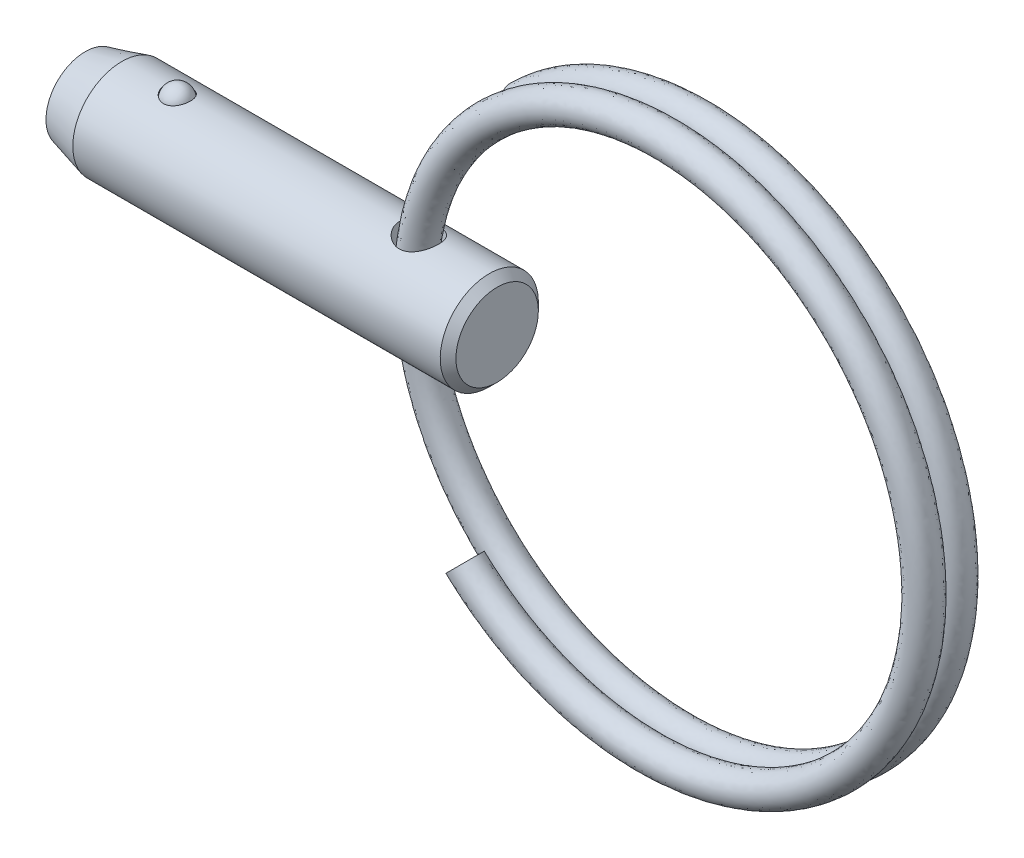
SolidWorks part; units mm, degrees
ref_plane "Front" through (0, 0, 0) normal (0, 0, 1) x (1, 0, 0)
ref_plane "Top" through (0, 0, 0) normal (0, 1, 0) x (1, 0, 0)
ref_plane "Right" through (0, 0, 0) normal (1, 0, 0) x (0, 0, -1)
sketch "Sketch1" plane through (0, 0, 0) normal (0, 0, 1) x (1, 0, 0)
  line L0 (9.9949, 2.0003) -> (9.6139, 2.3812)
  line L1 (9.6139, 2.3812) -> (9.9949, 2.3812) construction
  line L4 (9.9949, 2.0003) -> (9.9949, 0)
  line L5 (9.9949, 2.3812) -> (9.9949, 2.0003) construction
  line L16 (9.6139, 2.3812) -> (-8.2175, 2.3812)
  line L17 (-9.9949, 2.3812) -> (-9.9949, 1.905) construction
  line L19 (-8.2175, 2.3812) -> (-9.9949, 2.3812) construction
  line L22 (-9.9949, -2.3813) -> (-8.2175, -2.3812) construction
  line L23 (-5.5275, 2.1431) -> (-5.5275, -2.1431) construction
  line L24 (-9.9949, 0) -> (9.9949, 0)
  line L27 (9.9949, 0) -> (11.9952, 0) construction
  line L29 (-9.9949, 0) -> (-9.9949, -1.905) construction
  line L36 (5.2451, 0) -> (5.2451, 2.3812) construction
  line L37 (-9.9949, 1.905) -> (-9.9949, 0)
  line L38 (-8.2175, -2.3812) -> (9.9949, -2.3813) construction
  line L39 (-9.9949, -1.905) -> (-9.9949, -2.3813) construction
  line L40 (-8.2175, 2.3812) -> (-9.9949, 1.905)
  line L42 (-8.2175, -2.3812) -> (-9.9949, -1.905) construction
  line L43 (-8.2175, 2.3812) -> (-8.2175, -2.3812) construction
  circle A2 centre (-5.5275, 2.1431) radius 0.6572 construction
  point P35 (-4.9149, 2.3812)
  dimension "A1" = 15
revolve "Revolve1" add sketch "Sketch1" angle 360 about L27
sketch "Sketch2" plane through (0, 0, 0) normal (0, 0, 1) x (1, 0, 0)
  line L0 (-4.8448, 2.1431) -> (-6.2101, 2.1431)
  line L1 (-5.5275, 2.8003) -> (-5.5275, 2.8257) construction
  line L2 (-4.8448, 2.1431) -> (-3.4796, 2.1431) construction
  circle A0 centre (-5.5275, 2.1431) radius 0.6572 construction
  circle A1 centre (-5.5275, 2.1431) radius 0.6572 construction
  arc A2 (-6.2101, 2.1431) -> (-4.8448, 2.1431) centre (-5.5275, 2.1431) cw
  dimension "D1" = 0.0254
revolve "Cut-Revolve1" cut sketch "Sketch2" angle 360 about L2
sketch "Sketch3" plane through (0, 0, 0) normal (0, 0, 1) x (1, 0, 0)
  line L0 (-4.8702, 2.1431) -> (-6.1847, 2.1431)
  line L1 (-4.8702, 2.1431) -> (-3.5558, 2.1431) construction
  circle A0 centre (-5.5275, 2.1431) radius 0.6572 construction
  arc A1 (-4.8702, 2.1431) -> (-6.1847, 2.1431) centre (-5.5275, 2.1431) ccw
revolve "Revolve2" add sketch "Sketch3" angle 360 about L1
sketch "Sketch4" plane through (0, 0, 0) normal (0, 0, 1) x (1, 0, 0)
  line L1 (6.1976, -2.3812) -> (7.1501, -2.3812)
  line L2 (6.1976, -2.3812) -> (6.1976, 2.3812)
  line L3 (6.1976, 2.3812) -> (7.1501, 2.3812)
  line L4 (7.1501, -2.3812) -> (7.1501, 2.3812)
  line L5 (6.1976, -2.3812) -> (6.1976, -3.3338) construction
  line L6 (7.1501, 2.3812) -> (9.9949, 2.3812) construction
  line L8 (5.2451, -2.3812) -> (5.2451, 2.3812) construction
  line L9 (5.2451, 0) -> (6.1976, 0) construction
  line L11 (6.1976, 0) -> (7.1501, 0) construction
  line L12 (9.6139, 2.3812) -> (-8.2175, 2.3812) construction
  line L14 (-8.2175, -2.3812) -> (9.9949, -2.3812) construction
  dimension "D1" = 1.905
revolve "Cut-Revolve2" cut sketch "Sketch4" angle 360 about L2
sketch "Sketch5" plane through (0, 0, 0) normal (0, 0, 1) x (1, 0, 0)
  line L0 (0, 0) -> (5.3156, 0) construction
  line L1 (5.3156, 0) -> (5.3156, 2.3812) construction
  line L2 (9.6139, 2.3812) -> (-8.2175, 2.3812) construction
  line L3 (18.7776, 0) -> (32.2396, 0) construction
  line L4 (7.1501, 2.3812) -> (7.0796, 2.3812) construction
  line L5 (6.1976, 2.3812) -> (7.1501, 2.3812) construction
  line L6 (5.5279, 2.3812) -> (5.5279, -2.3812) construction
  line L7 (5.3156, 2.3812) -> (5.2451, 2.3812) construction
  line L8 (6.1976, -2.3812) -> (7.1501, -2.3812) construction
  line L9 (5.5279, -2.3812) -> (7.1501, -2.3812) construction
  line L10 (5.3156, 0) -> (18.7776, 0) construction
  line L12 (7.0796, 2.3812) -> (5.5279, 2.3812) construction
  line L13 (18.7776, 11.938) -> (18.7776, 13.462) construction
  circle A0 centre (18.7776, 0) radius 13.462
  circle A1 centre (18.7776, 0) radius 11.938 construction
  circle A2 centre (18.7776, 0) radius 12.7 construction
  point P26 (18.7776, 12.7)
curve "Helix/Spiral1" pitch 1.5494 height 1.3557 radius 13.462 left hand yes centre (18.7776, 0, 0) axis (0, 0, -1) start towards (1, 0, 0)
sketch "Sketch6" plane through (114.0038, 0, 0) normal (0, 1, 0) x (0, 0, -1)
  line L0 (0, 107.1642) -> (0, 107.9262) construction
  line L1 (0, 107.9262) -> (0, 108.6882) construction
  circle A0 centre (0, 107.9262) radius 0.762
  dimension "D1" = 1.524
sketch "Sketch7" plane through (0, 0, 0) normal (0, 0, 1) x (1, 0, 0)
  circle A0 centre (18.7776, 0) radius 13.462 construction
  circle A1 centre (18.7776, 0) radius 13.462
curve "Helix/Spiral2" pitch 1.5494 height 1.3557 radius 13.462 left hand yes centre (18.7776, 0, 0) axis (0, 0, 1) start towards (1, 0, 0)
sweep "Sweep1" add profiles "Sketch6" path "Helix/Spiral1"
sweep "Sweep2" add profiles "Sketch6<2>" path "Helix/Spiral2"
sketch "Sketch6<2>" plane through (114.0038, 0, 0) normal (0, 1, 0) x (0, 0, -1) same geometry as "Sketch6"
equation "\"D12@Sketch1\"=\"A@Sketch1\" * 0.80"
equation "\"D2@Sketch1\"=\"A@Sketch1\" * 0.9"
equation "\"D1@Sketch4\" = \"A@Sketch1\" / 2.5"
equation "\"Ring OD@Sketch5\" = \"R Ring Dia@Sketch5\" * 0.06"
equation "\"D4@Helix/Spiral1\"=\"Ring OD@Sketch5\" + 0.001"
equation "\"D1@Sketch6\"=\"Ring OD@Sketch5\""
equation "\"D4@Helix/Spiral2\" = \"D4@Helix/Spiral1\""
equation "\"D5@Helix/Spiral2\" = \"D5@Helix/Spiral1\""
